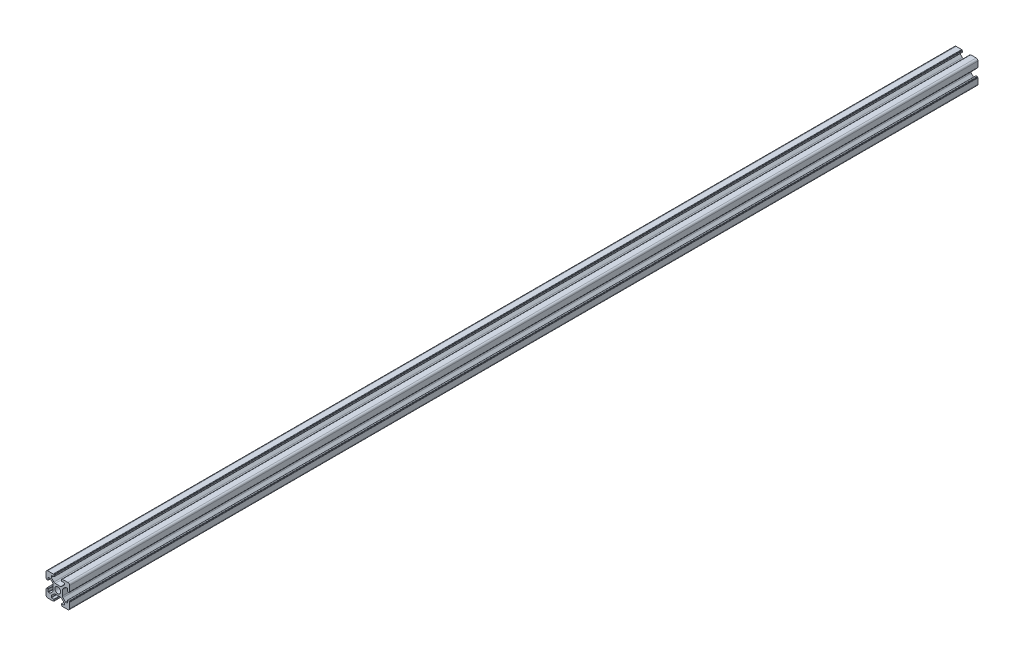
SolidWorks part; units mm, degrees
material "1060 Alloy"
ref_plane "Front Plane" through (0, 0, 0) normal (0, 0, 1) x (1, 0, 0)
ref_plane "Top Plane" through (0, 0, 0) normal (0, 1, 0) x (1, 0, 0)
ref_plane "Right Plane" through (0, 0, 0) normal (1, 0, 0) x (0, 0, -1)
sketch "Sketch1" plane through (0, 0, 0) normal (0, 0, 1) x (1, 0, 0)
  line L0 (3.8995, 3.9005) -> (10.4604, 10.4604) construction
  line L2 (-3.9002, 2.2177) -> (-3.9002, -2.2208)
  line L5 (-3.9005, 3.899) -> (3.9001, -3.8986) construction
  line L6 (-3.9, -3.901) -> (3.8995, 3.9005) construction
  line L7 (-0.0002, 10) -> (-0.0002, -9.9996) construction
  line L8 (-0.0002, -9.9996) -> (-0.0002, 10) construction
  line L9 (5.5006, 6.5619) -> (3.2793, 4.3405)
  line L14 (-10.0002, 9.9996) -> (9.9994, -10) construction
  line L15 (-9.9999, -10.0001) -> (9.9998, 10) construction
  line L16 (6.5613, 5.5012) -> (4.3401, 3.28)
  line L17 (-5.5002, 6.5603) -> (-3.279, 4.3391)
  line L18 (-6.5609, 5.4996) -> (-4.3395, 3.2783)
  line L19 (7.9206, 5.5012) -> (6.5613, 5.5012)
  line L20 (8.2006, 3.3812) -> (8.2006, 5.2212)
  line L21 (9.4206, 3.1012) -> (8.4806, 3.1012)
  line L22 (9.7006, 3.6012) -> (9.7006, 3.3812)
  line L23 (-8.5002, 9.9996) -> (-3.8802, 9.9996)
  line L24 (-3.6002, 9.7196) -> (-3.6002, 9.6996)
  line L25 (-3.6002, 9.6996) -> (-3.3802, 9.6996)
  line L26 (-3.1002, 9.4196) -> (-3.1002, 8.4796)
  line L27 (-3.3802, 8.1996) -> (-5.2202, 8.1996)
  line L28 (-5.5002, 7.9196) -> (-5.5002, 6.5603)
  line L29 (-7.9202, 5.4996) -> (-6.5609, 5.4996)
  line L30 (-8.2002, 3.3796) -> (-8.2002, 5.2196)
  line L31 (-9.4202, 3.0996) -> (-8.4802, 3.0996)
  line L32 (-9.7202, 3.5996) -> (-9.7002, 3.5996)
  line L33 (-9.7002, 3.5996) -> (-9.7002, 3.3796)
  line L34 (-10.0002, 8.4996) -> (-10.0002, 3.8796)
  line L35 (10.0006, 8.5012) -> (10.0006, 3.8812)
  line L36 (8.5006, 10.0012) -> (3.8806, 10.0012)
  line L37 (3.6006, 9.7012) -> (3.3806, 9.7012)
  line L38 (3.1006, 9.4212) -> (3.1006, 8.4812)
  line L39 (3.3806, 8.2012) -> (5.2206, 8.2012)
  line L40 (5.5006, 7.9212) -> (5.5006, 6.5619)
  line L41 (6.5629, -5.4996) -> (4.3415, -3.2783)
  line L42 (5.5022, -6.5603) -> (3.281, -4.3391)
  line L43 (5.5022, -7.9196) -> (5.5022, -6.5603)
  line L44 (3.3822, -8.1996) -> (5.2222, -8.1996)
  line L45 (3.1022, -9.4196) -> (3.1022, -8.4796)
  line L46 (3.6022, -9.6996) -> (3.3822, -9.6996)
  line L47 (8.5022, -9.9996) -> (3.8822, -9.9996)
  line L48 (10.0022, -8.4996) -> (10.0022, -3.8796)
  line L49 (9.7022, -3.5996) -> (9.7022, -3.3796)
  line L50 (9.4222, -3.0996) -> (8.4822, -3.0996)
  line L51 (8.2022, -3.3796) -> (8.2022, -5.2196)
  line L52 (7.9222, -5.4996) -> (6.5629, -5.4996)
  line L53 (-5.4986, -6.5619) -> (-3.2773, -4.3405)
  line L54 (-6.5593, -5.5012) -> (-4.3395, -3.2814)
  line L55 (-7.9186, -5.5012) -> (-6.5593, -5.5012)
  line L56 (-8.1986, -3.3812) -> (-8.1986, -5.2212)
  line L57 (-9.4186, -3.1012) -> (-8.4786, -3.1012)
  line L58 (-9.6986, -3.6012) -> (-9.6986, -3.3812)
  line L59 (-9.9986, -8.5012) -> (-9.9986, -3.8812)
  line L60 (-8.4986, -10.0012) -> (-3.8786, -10.0012)
  line L61 (-3.5986, -9.7012) -> (-3.3786, -9.7012)
  line L62 (-3.0986, -9.4212) -> (-3.0986, -8.4812)
  line L63 (-3.3786, -8.2012) -> (-5.2186, -8.2012)
  line L64 (-5.4986, -7.9212) -> (-5.4986, -6.5619)
  line L65 (-2.233, 3.8998) -> (2.2187, 3.9012)
  line L66 (3.9008, 2.234) -> (3.9022, -2.2177)
  line L67 (2.235, -3.8998) -> (-2.2167, -3.9012)
  line L68 (3.6006, 9.7212) -> (3.6006, 9.6996)
  line L69 (9.7006, 3.6012) -> (9.7206, 3.6012)
  line L70 (-9.6986, -3.6012) -> (-9.7186, -3.6012)
  line L71 (-3.5986, -9.7012) -> (-3.5986, -9.7212)
  line L72 (3.6022, -9.6996) -> (3.6022, -9.7196)
  line L73 (9.7222, -3.5996) -> (9.7022, -3.5996)
  arc A0 (-3.6002, 9.7196) -> (-3.8802, 9.9996) centre (-3.8802, 9.7196) ccw
  arc A1 (-3.3802, 9.6996) -> (-3.1002, 9.4196) centre (-3.3802, 9.4196) cw
  arc A2 (-3.1002, 8.4796) -> (-3.3802, 8.1996) centre (-3.3802, 8.4796) cw
  arc A3 (-10.0002, 8.4996) -> (-8.5002, 9.9996) centre (-8.5002, 8.4996) cw
  arc A4 (-8.2002, 3.3796) -> (-8.4802, 3.0996) centre (-8.4802, 3.3796) cw
  arc A5 (-9.4202, 3.0996) -> (-9.7002, 3.3796) centre (-9.4202, 3.3796) cw
  arc A6 (-9.7202, 3.5996) -> (-10.0002, 3.8796) centre (-9.7202, 3.8796) cw
  arc A7 (-3.279, 4.3391) -> (-2.233, 3.8998) centre (-2.2183, 5.3997) ccw
  arc A8 (-4.3395, 3.2783) -> (-3.9002, 2.2177) centre (-5.4002, 2.2177) cw
  arc A9 (-7.9202, 5.4996) -> (-8.2002, 5.2196) centre (-7.9202, 5.2196) ccw
  arc A10 (-5.2202, 8.1996) -> (-5.5002, 7.9196) centre (-5.2202, 7.9196) ccw
  arc A12 (-4.3395, -3.2814) -> (-3.9002, -2.2208) centre (-5.4002, -2.2208) ccw
  arc A13 (8.2006, 5.2212) -> (7.9206, 5.5012) centre (7.9206, 5.2212) ccw
  arc A14 (8.4806, 3.1012) -> (8.2006, 3.3812) centre (8.4806, 3.3812) cw
  arc A15 (9.7006, 3.3812) -> (9.4206, 3.1012) centre (9.4206, 3.3812) cw
  arc A16 (9.7206, 3.6012) -> (10.0006, 3.8812) centre (9.7206, 3.8812) ccw
  arc A17 (8.5006, 10.0012) -> (10.0006, 8.5012) centre (8.5006, 8.5012) cw
  arc A18 (3.6006, 9.7212) -> (3.8806, 10.0012) centre (3.8806, 9.7212) cw
  arc A19 (3.1006, 9.4212) -> (3.3806, 9.7012) centre (3.3806, 9.4212) cw
  arc A20 (3.3806, 8.2012) -> (3.1006, 8.4812) centre (3.3806, 8.4812) cw
  arc A21 (5.5006, 7.9212) -> (5.2206, 8.2012) centre (5.2206, 7.9212) ccw
  arc A22 (3.2793, 4.3405) -> (2.2187, 3.9012) centre (2.2187, 5.4012) cw
  arc A23 (4.3401, 3.28) -> (3.9008, 2.234) centre (5.4007, 2.2193) ccw
  arc A25 (5.2222, -8.1996) -> (5.5022, -7.9196) centre (5.2222, -7.9196) ccw
  arc A26 (3.1022, -8.4796) -> (3.3822, -8.1996) centre (3.3822, -8.4796) cw
  arc A27 (3.3822, -9.6996) -> (3.1022, -9.4196) centre (3.3822, -9.4196) cw
  arc A28 (3.6022, -9.7196) -> (3.8822, -9.9996) centre (3.8822, -9.7196) ccw
  arc A29 (10.0022, -8.4996) -> (8.5022, -9.9996) centre (8.5022, -8.4996) cw
  arc A30 (9.7222, -3.5996) -> (10.0022, -3.8796) centre (9.7222, -3.8796) cw
  arc A31 (9.4222, -3.0996) -> (9.7022, -3.3796) centre (9.4222, -3.3796) cw
  arc A32 (8.2022, -3.3796) -> (8.4822, -3.0996) centre (8.4822, -3.3796) cw
  arc A33 (7.9222, -5.4996) -> (8.2022, -5.2196) centre (7.9222, -5.2196) ccw
  arc A34 (4.3415, -3.2783) -> (3.9022, -2.2177) centre (5.4022, -2.2177) cw
  arc A35 (3.281, -4.3391) -> (2.235, -3.8998) centre (2.2203, -5.3997) ccw
  circle A36 centre (0.001, -0.001) radius 2.5 construction
  arc A37 (-8.1986, -5.2212) -> (-7.9186, -5.5012) centre (-7.9186, -5.2212) ccw
  arc A38 (-8.4786, -3.1012) -> (-8.1986, -3.3812) centre (-8.4786, -3.3812) cw
  arc A39 (-9.6986, -3.3812) -> (-9.4186, -3.1012) centre (-9.4186, -3.3812) cw
  arc A40 (-9.7186, -3.6012) -> (-9.9986, -3.8812) centre (-9.7186, -3.8812) ccw
  arc A41 (-8.4986, -10.0012) -> (-9.9986, -8.5012) centre (-8.4986, -8.5012) cw
  arc A42 (-3.5986, -9.7212) -> (-3.8786, -10.0012) centre (-3.8786, -9.7212) cw
  arc A43 (-3.0986, -9.4212) -> (-3.3786, -9.7012) centre (-3.3786, -9.4212) cw
  arc A44 (-3.3786, -8.2012) -> (-3.0986, -8.4812) centre (-3.3786, -8.4812) cw
  arc A45 (-5.4986, -7.9212) -> (-5.2186, -8.2012) centre (-5.2186, -7.9212) ccw
  arc A46 (-3.2773, -4.3405) -> (-2.2167, -3.9012) centre (-2.2167, -5.4012) cw
  arc A48 (-4.3381, -3.28) -> (-3.8988, -2.234) centre (-5.3987, -2.2193) ccw [skipped]
  point P0 (0, 0)
  point P9 (-0.0002, 0.0002)
  point P12 (-0.0003, -0.0003)
  point P43 (-3.6002, 9.9996)
  point P46 (-3.1002, 9.6996)
  point P49 (-3.1002, 8.1996)
  point P55 (-8.2002, 3.0996)
  point P58 (-9.7002, 3.0996)
  point P61 (-10.0002, 3.5996)
  point P64 (-2.8395, 3.8996)
  point P67 (-3.9002, 2.839)
  point P70 (-8.2002, 5.4996)
  point P73 (-5.5002, 8.1996)
  point P184 (0.001, 0)
  dimension "D14" = 0.28
  dimension "D15" = 0.28
  dimension "D16" = 0.28
  dimension "D17" = 1.5
  dimension "D18" = 0.28
  dimension "D19" = 1.5
  dimension "D20" = 1.5
  dimension "D21" = 0.28
  dimension "D23" = 5
  dimension "D27" = 1.5
  dimension "D1" = 7.8
  dimension "D2" = 7.8
  dimension "D3" = 3.1
  dimension "D4" = 3.6
  dimension "D5" = 20
  dimension "D6" = 20
  dimension "D7" = 0.75
  dimension "D8" = 1.8
  dimension "D9" = 5.5
  dimension "D10" = 6.4
  dimension "D11" = 6.4
  dimension "D12" = 3.7627
  dimension "D13" = 0.3
  dimension "D24" = 4.62
  dimension "D25" = 3.9005
  dimension "D26" = 7.801
  dimension "D22" = 4
extrude "Boss-Extrude1" add sketch "Sketch1" along normal blind 770 contours L53 A46 L67 A35 L42 L43 A25 L44 A26 L45 A27 L46 L72 A28 L47 A29 L48 A30 L73 L49 A31 L50 A32 L51 A33 L52 L41 A34 L66 A23 L16 L19 A13 L20 A14 L21 A15 L22 L69 A16 L35 A17 L36 A18 L68 L37 A19 L38 A20 region at (0.0009, 0, 0)
sketch3d "3DSketch2"
  circle A0 centre (0, 0, 0) radius 2.5
  point P2 (0, 0, 2.5)
extrude "Cut-Extrude1" cut sketch "3DSketch2" along direction (0, 0, 1) on the side of the normal through all contours A0
